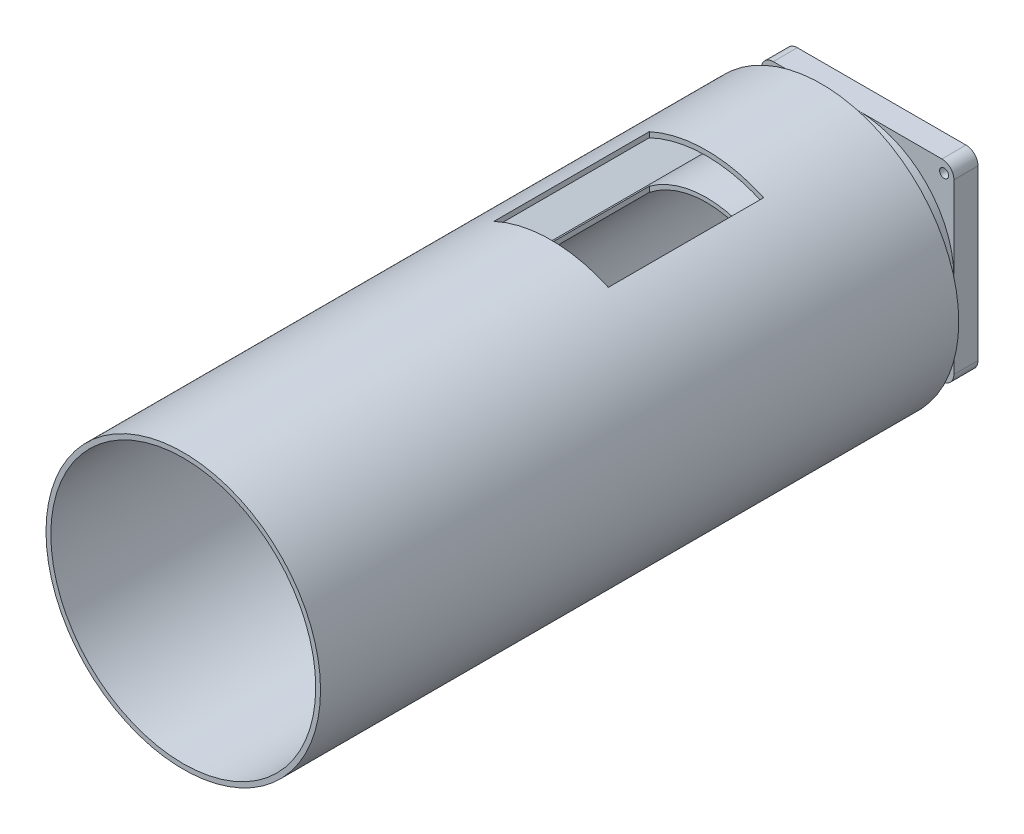
SolidWorks part; units mm, degrees
ref_plane "前视基准面" through (0, 0, 0) normal (0, 0, 1) x (1, 0, 0)
ref_plane "上视基准面" through (0, 0, 0) normal (0, 1, 0) x (1, 0, 0)
ref_plane "右视基准面" through (0, 0, 0) normal (1, 0, 0) x (0, 0, -1)
ref_axis "基准轴1" through (0, 0, 20.9) along (0, 0, -1)
ref_plane "基准面1" through (55, 0, 0) normal (1, 0, 0) x (0, 0, -1)
sketch "草图7" plane through (0, 0, 0) normal (0, 0, 1) x (1, 0, 0)
  line L1 (-40, 40) -> (40, 40)
  line L2 (-40, 40) -> (-40, -40)
  line L3 (-40, -40) -> (40, -40)
  line L4 (40, 40) -> (40, -40)
  line L5 (-40, 40) -> (40, -40) construction
  line L6 (-40, -40) -> (40, 40) construction
  circle A0 centre (0, 0) radius 50.7986 construction
  circle A1 centre (-35.92, 35.92) radius 1.875
  circle A2 centre (35.92, 35.92) radius 1.875
  circle A3 centre (35.92, -35.92) radius 1.875
  circle A4 centre (-35.92, -35.92) radius 1.875
  circle A5 centre (0, 0) radius 38.25
  point P0 (0, 0)
  point P17 (0, 38.25)
  dimension "D2" = 3.75
  dimension "D4" = 76.5
  dimension "D1" = 80
  dimension "D3" = 71.84
extrude "凸台-拉伸3" [suppressed] add sketch "草图7" along normal mid plane 25 contours A5 | L4 L1 L2 L3 A5 A4 A3 A2 A1
fillet "圆角1" [suppressed] radius 5
sketch "草图2" [suppressed] plane through (0, 0, 0) normal (0, 1, 0) x (1, 0, 0)
  line L0 (0, 12.5) -> (0, -12.5) construction
  line L1 (0, 0) -> (89.5, 0) construction
  line L3 (89.5, -8.5) -> (39.5, -8.5)
  line L4 (89.5, -8.5) -> (89.5, 8.5)
  line L5 (89.5, 8.5) -> (39.5, 8.5)
  line L6 (39.5, -8.5) -> (39.5, 8.5)
  line L7 (38.25, 4.5) -> (17.5, 4.5)
  line L8 (38.25, 4.5) -> (38.25, -12.5)
  line L9 (38.25, -12.5) -> (14.5, -12.5)
  line L10 (14.5, -12.5) -> (0, -12.5)
  line L12 (17.5, 4.5) -> (17.5, -9.5)
  line L14 (-35, 12.5) -> (35, 12.5) construction
  arc A2 (14.5, -12.5) -> (17.5, -9.5) centre (14.5, -9.5) ccw
  point P14 (38.25, 0)
  dimension "D8" = 3
  dimension "D1" = 4
  dimension "D2" = 79
  dimension "D3" = 50
  dimension "D4" = 8
  dimension "D6" = 35
revolve "切除-旋转1" [suppressed] cut sketch "草图2" angle 360 about L0
sketch "草图3" [suppressed] plane through (0, 0, 0) normal (0, 0, 1) x (1, 0, 0)
  line L0 (0, 0) -> (0, 17.5) construction
  line L1 (8.0065, 15.561) -> (38.25, 0)
  line L3 (9.473, -14.7144) -> (-19.125, -33.1255)
  line L4 (-17.4795, -0.8466) -> (-19.125, 33.1255)
  line L5 (37.8635, -5.4241) -> (16.6094, 5.5116)
  circle A0 centre (0, 0) radius 17.5
  arc A1 (-19.125, -33.1255) -> (38.25, 0) centre (0, 0) ccw
  circle A2 centre (0, 0) radius 38.25 construction
  point P17 (0, 0)
  dimension "D2" = 5
  dimension "D1" = 3
extrude "切除-拉伸1" [suppressed] cut sketch "草图3" against normal through all contours L3 A1 L5 A0
pattern_circular "阵列(圆周)1" [suppressed] count 3 over 360 about axis through (0, 0, 20.9) along (0, 0, -1) of bodies 108
sketch "草图4" plane through (0, 0, 0) normal (1, 0, 0) x (0, 0, -1)
  line L0 (-14.3137, 11.3137) -> (8.3137, -11.3137) construction
  line L1 (-13.4298, 12.1976) -> (9.1976, -10.4298)
  line L2 (-15.1976, 10.4298) -> (7.4298, -12.1976)
  line L3 (-20.9, 0) -> (20.9, 0) construction
  arc A0 (-13.4298, 12.1976) -> (-15.1976, 10.4298) centre (-14.3137, 11.3137) ccw
  arc A1 (7.4298, -12.1976) -> (9.1976, -10.4298) centre (8.3137, -11.3137) ccw
  point P2 (-3, 0)
  dimension "D1" = 2.5
  dimension "D2" = 45
  dimension "D3" = 32
  dimension "D4" = 3
sketch "草图5" plane through (55, 0, 0) normal (1, 0, 0) x (0, 0, -1)
  line L0 (-11.8163, 50) -> (5.8163, -50) construction
  line L1 (-10.5853, 50.2171) -> (7.0474, -49.7829)
  line L2 (-13.0474, 49.7829) -> (4.5853, -50.2171)
  line L3 (-20.9, 0) -> (20.9, 0) construction
  arc A0 (-10.5853, 50.2171) -> (-13.0474, 49.7829) centre (-11.8163, 50) ccw
  arc A1 (4.5853, -50.2171) -> (7.0474, -49.7829) centre (5.8163, -50) ccw
  arc A2 (-13.4298, 12.1976) -> (-15.1976, 10.4298) centre (-14.3137, 11.3137) ccw construction
  point P2 (-3, 0)
  dimension "D1" = 80
  dimension "D2" = 100
loft "放样1" [suppressed] add profiles "草图4", "草图5"
sketch "草图6" [suppressed] plane through (0, 0, 0) normal (0, 0, 1) x (1, 0, 0)
  line L0 (0, 11.3137) -> (0, -11.3137) construction
  line L1 (0, 0) -> (19.8943, -19.8943)
  line L2 (0, 0) -> (19.3185, 5.1764)
  line L3 (0, -65.4206) -> (0, 62.9965) construction
  line L5 (0, 0) -> (112.9869, 0) construction
  arc A0 (37.2417, -0.7851) -> (32.5394, -18.1314) centre (0, 0) cw
  arc A1 (32.466, 1.6957) -> (19.3185, 5.1764) centre (27.2947, 8.7333) cw
  arc A2 (32.5394, -18.1314) -> (19.8943, -19.8943) centre (25.5511, -14.2374) cw
  arc A3 (37.2417, -0.7851) -> (32.466, 1.6957) centre (34.2424, -0.7219) ccw
  circle A4 centre (0, 0) radius 38.25 construction
  point P17 (35.9807, 9.641)
  dimension "D1" = 60
  dimension "D3" = 8
  dimension "D4" = 1
  dimension "D6" = 3
  dimension "D2" = 45
  dimension "D5" = 20
extrude "切除-拉伸2" [suppressed] cut sketch "草图6" against normal mid plane 100 flip side to cut contours A0 A3 A1 L2 L1 A2
pattern_circular "阵列(圆周)3" [suppressed] count 5 over 360 about axis through (0, 0, 20.9) along (0, 0, -1) of bodies 111 112
fillet "圆角2" [suppressed] radius 3
sketch "Sketch1" plane through (0, 0, 0) normal (0, 0, 1) x (1, 0, 0)
  line L0 (0, -40) -> (0, 40) construction
  line L1 (-40, 0) -> (40, 0) construction
  line L8 (35, 40) -> (-35, 40)
  line L9 (-40, 35.0014) -> (-40, -34.9986)
  line L10 (-35, -40) -> (35, -40)
  line L11 (40, -34.9986) -> (40, 35.0014)
  arc A9 (-35, 40) -> (-40, 35.0014) centre (-35, 35) ccw
  arc A10 (-40, -34.9986) -> (-35, -40) centre (-35, -35) ccw
  arc A11 (35, -40) -> (40, -34.9986) centre (35, -35) ccw
  arc A12 (40, 35.0014) -> (35, 40) centre (35, 35) ccw
  circle A13 centre (-35.92, 35.336) radius 1.875
  circle A14 centre (-35.92, -35.92) radius 1.875
  circle A15 centre (35.92, 35.336) radius 1.875
  circle A16 centre (35.92, -35.92) radius 1.875
  circle A17 centre (0, 0) radius 38.25
  point P16 (0, 0)
  point P30 (0, 0)
  dimension "D2" = 5
  dimension "D3" = 3.75
  dimension "D6" = 76.5
  dimension "D10" = 5
  dimension "D1" = 70
  dimension "D4" = 40
  dimension "D5" = 50.7986
  dimension "D7" = 40
  dimension "D8" = 1.3011
  dimension "D9" = 35.336
extrude "Boss-Extrude1" add sketch "Sketch1" along normal mid plane 10 separate body
sketch "Sketch2" plane through (0, 0, 5) normal (0, 0, 1) x (1, 0, 0)
  circle A0 centre (0, 0) radius 40
  circle A1 centre (0, 0) radius 38.25 construction
  circle A2 centre (0, 0) radius 38.25
  dimension "D1" = 80
extrude "Boss-Extrude2" add sketch "Sketch2" along normal blind 200 separate body
ref_plane "Plane1" through (0, 0, 20) normal (0, 0, 1) x (1, 0, 0)
sketch "Sketch3" plane through (0, 0, 20) normal (0, 0, 1) x (1, 0, 0)
  line L0 (0, -38.25) -> (0, -55) construction
  line L1 (-1.75, -38.2099) -> (-1.75, -54.9722)
  line L2 (1.75, -38.2099) -> (1.75, -54.9722)
  line L3 (-33.1255, 19.125) -> (-47.6314, 27.5) construction
  line L4 (-32.2158, 20.6205) -> (-46.7323, 29.0016)
  line L5 (-33.9658, 17.5894) -> (-48.4823, 25.9705)
  line L6 (33.1255, 19.125) -> (47.6314, 27.5) construction
  line L7 (33.9658, 17.5894) -> (48.4823, 25.9705)
  line L8 (32.2158, 20.6205) -> (46.7323, 29.0016)
  circle A0 centre (0, 0) radius 55
  circle A1 centre (0, 0) radius 57
  circle A2 centre (0, 0) radius 38.25 construction
  circle A3 centre (0, 0) radius 38.25
  dimension "D1" = 110
  dimension "D3" = 1.75
  dimension "D2" = 2
  dimension "D4" = 3
extrude "Boss-Extrude3" add sketch "Sketch3" along normal through all separate body contours A1 A0 | A3 L1 A0 L2 | A3 L4 A0 L5 | A3 L7 A0 L8 region at (0, -46.6137, 20) region at (-40.3686, 23.3068, 20) region at (40.3686, 23.3068, 20) region at (-55.3878, 0, 20)
sketch "Sketch4" plane through (0, 0, 0) normal (0, 1, 0) x (1, 0, 0)
  line L0 (-57, -205) -> (57, -205) construction
  line L1 (57, -20) -> (-57, -20) construction
  line L2 (-57, -205) -> (57, -205)
  line L3 (57, -20) -> (-57, -20)
  line L4 (0, 5) -> (0, -205) construction
  line L6 (-23.75, -67.75) -> (23.75, -67.75)
  line L7 (-23.75, -67.75) -> (-23.75, -132.25)
  line L8 (-23.75, -132.25) -> (23.75, -132.25)
  line L9 (23.75, -67.75) -> (23.75, -132.25)
  line L10 (-23.75, -67.75) -> (23.75, -132.25) construction
  line L11 (-23.75, -132.25) -> (23.75, -67.75) construction
  line L13 (35, 5) -> (-35, 5) construction
  line L14 (35, 5) -> (-35, 5)
  point P4 (0, -100)
  point P7 (0, -100)
  point P20 (0, 5)
  dimension "D1" = 47.5
  dimension "D2" = 64.5
extrude "Cut-Extrude1" cut sketch "Sketch4" along normal through all contours L9 L6 L7 L8 region at (0, 0, 100)
ref_plane "Plane2" through (0, 0, 132.25) normal (0, 0, -1) x (-1, 0, 0)
sketch "Sketch5" plane through (0, 0, 132.25) normal (0, 0, -1) x (-1, 0, 0)
  line L0 (-23.75, 32.186) -> (-23.75, 29.9833) construction
  line L1 (23.75, 29.9833) -> (23.75, 32.186) construction
  line L2 (23.75, 49.6078) -> (23.75, 51.8164) construction
  line L3 (-23.75, 51.8164) -> (-23.75, 49.6078) construction
  line L4 (-23.75, 32.186) -> (-23.75, 29.9833)
  line L5 (23.75, 29.9833) -> (23.75, 32.186)
  line L6 (23.75, 49.6078) -> (23.75, 51.8164)
  line L7 (-23.75, 51.8164) -> (-23.75, 49.6078)
  line L8 (-23.75, 49.6078) -> (-23.75, 32.186)
  line L9 (23.75, 49.6078) -> (23.75, 32.186)
  arc A0 (23.75, 32.186) -> (-23.75, 32.186) centre (0, 0) ccw construction
  arc A1 (23.75, 29.9833) -> (-23.75, 29.9833) centre (0, 0) ccw construction
  arc A2 (23.75, 51.8164) -> (-23.75, 51.8164) centre (0, 0) ccw construction
  arc A3 (23.75, 49.6078) -> (-23.75, 49.6078) centre (0, 0) ccw construction
  arc A4 (23.75, 32.186) -> (-23.75, 32.186) centre (0, 0) ccw
  arc A5 (23.75, 29.9833) -> (-23.75, 29.9833) centre (0, 0) ccw
  arc A6 (23.75, 51.8164) -> (-23.75, 51.8164) centre (0, 0) ccw
  arc A7 (23.75, 49.6078) -> (-23.75, 49.6078) centre (0, 0) ccw
extrude "Boss-Extrude4" add sketch "Sketch5" against normal blind 2 contours L9 A7 L8 A4 region at (0, 45.287, 132.25)
sketch "Sketch6" plane through (0, 0, 205) normal (0, 0, 1) x (1, 0, 0)
  circle A0 centre (0, 0) radius 57 construction
  circle A1 centre (0, 0) radius 57
  circle A2 centre (0, 0) radius 55
  arc M6 (-46.7323, 29.0016) -> (46.7323, 29.0016) centre (0, 0) cw
  arc M10 (-1.75, -54.9722) -> (-48.4823, 25.9705) centre (0, 0) cw
  arc M14 (48.4823, 25.9705) -> (1.75, -54.9722) centre (0, 0) cw
  circle M16 centre (0, 0) radius 57
extrude "Boss-Extrude5" add sketch "Sketch6" along normal blind 80 contours A2 M16 M14 M10 M6 | A1 | A2 region at (-55.3878, 0, 205)
ref_plane "Plane3" through (0, 0, 100) normal (0, 0, -1) x (-1, 0, 0)
